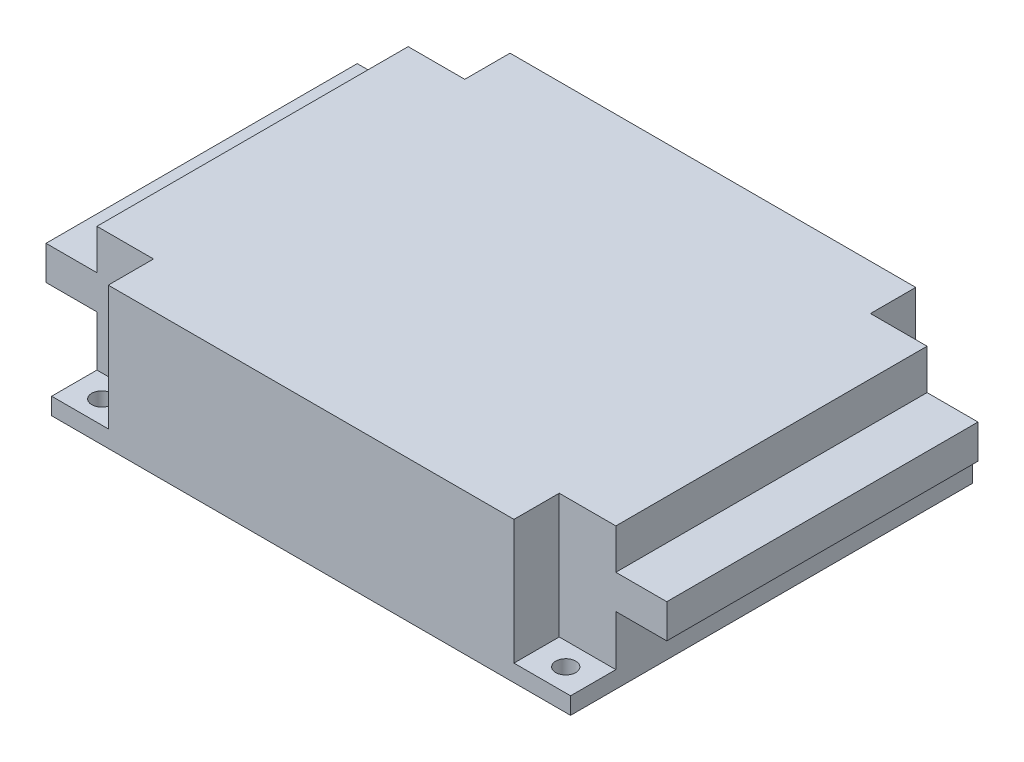
SolidWorks part; units mm, degrees
ref_plane "前视基准面" through (0, 0, 0) normal (0, 0, 1) x (1, 0, 0)
ref_plane "上视基准面" through (0, 0, 0) normal (0, 1, 0) x (1, 0, 0)
ref_plane "右视基准面" through (0, 0, 0) normal (1, 0, 0) x (0, 0, -1)
other "Configuration Table"
sketch "草图2" plane through (0, 0, 0) normal (0, 1, 0) x (1, 0, 0)
  line L4 (0, 60) -> (91.7, 60)
  line L9 (91.7, 60) -> (91.7, 49)
  line L10 (91.7, -11) -> (91.7, 0)
  line L11 (0, -11) -> (91.7, -11)
  line L12 (0, -11) -> (0, 0)
  line L13 (0, 51.9997) -> (10.0029, 51.9997)
  line L14 (10.0029, 51.9997) -> (10.0029, 60)
  line L15 (0, 60) -> (0, 51.9997)
  line L16 (0, 51.9997) -> (0, 49)
  line L17 (91.7, 51.9997) -> (81.6971, 51.9997)
  line L18 (81.6971, 51.9997) -> (81.6971, 60)
  line L19 (91.7, -2.9997) -> (81.6971, -2.9997)
  line L20 (81.6971, -2.9997) -> (81.6971, -11)
  line L21 (10.0029, -2.9997) -> (10.0029, -11)
  line L22 (0, -2.9997) -> (10.0029, -2.9997)
  line L23 (0, 49) -> (0, 0)
  line L24 (91.7, 49) -> (91.7, 0)
  circle A0 centre (4.8537, 55.9996) radius 1.7656
  circle A1 centre (86.8463, 55.9996) radius 1.7656
  circle A2 centre (86.8463, -6.9996) radius 1.7656
  circle A3 centre (4.8537, -6.9996) radius 1.7656
extrude "凸台-拉伸2" add sketch "草图2" along normal blind 3 contours L18 L17 L9 L4 A1 | L19 L20 L11 L10 A2 | L22 L12 L11 L21 A3 | L4 L15 L13 L14 A0 region at (5.0015, 0, -59.8719) region at (86.6985, 0, -59.8719) region at (5.0015, 0, 3.1278) region at (91.5719, 0, 6.9999)
extrude "凸台-拉伸3" add sketch "草图2<7>" along normal blind 25 contours L12 L22 L21 L11 L20 L19 L10 L9 L17 L18 L4 L14 L13 L16 region at (45.85, 0, -24.5)
sketch "草图2<7>" plane through (0, 0, 0) normal (0, 1, 0) x (1, 0, 0) same geometry as "草图2"
sketch "草图3" plane through (0, 0, 0) normal (1, 0, 0) x (0, 0, -1)
  line L0 (-2.9997, 17.9) -> (51.9997, 17.9)
  line L1 (-2.9997, 25) -> (-2.9997, 3) construction
  line L7 (51.9997, 25) -> (51.9997, 3) construction
  line L9 (-2.9997, 11.9) -> (51.9997, 11.9)
  line L10 (-2.9997, 11.9) -> (-2.9997, 17.9)
  line L11 (51.9997, 17.9) -> (51.9997, 11.9)
extrude "凸台-拉伸4" add sketch "草图3" against normal blind 9
ref_plane "基准面1" through (91.7, 0, 0) normal (1, 0, 0) x (0, 0, -1)
sketch "草图5" plane through (91.7, 0, 0) normal (1, 0, 0) x (0, 0, -1)
  line L0 (-2.9997, 17.9) -> (51.9997, 17.9)
  line L1 (-2.9997, 25) -> (-2.9997, 3) construction
  line L2 (-2.9997, 11.9) -> (-2.9997, 17.9)
  line L3 (-2.9997, 25) -> (-2.9997, 3) construction
  line L4 (51.9997, 25) -> (51.9997, 3) construction
  line L5 (51.9997, 17.9) -> (51.9997, 11.9)
  line L6 (51.9997, 11.9) -> (-2.9997, 11.9)
extrude "凸台-拉伸6" add sketch "草图5" along normal blind 9
